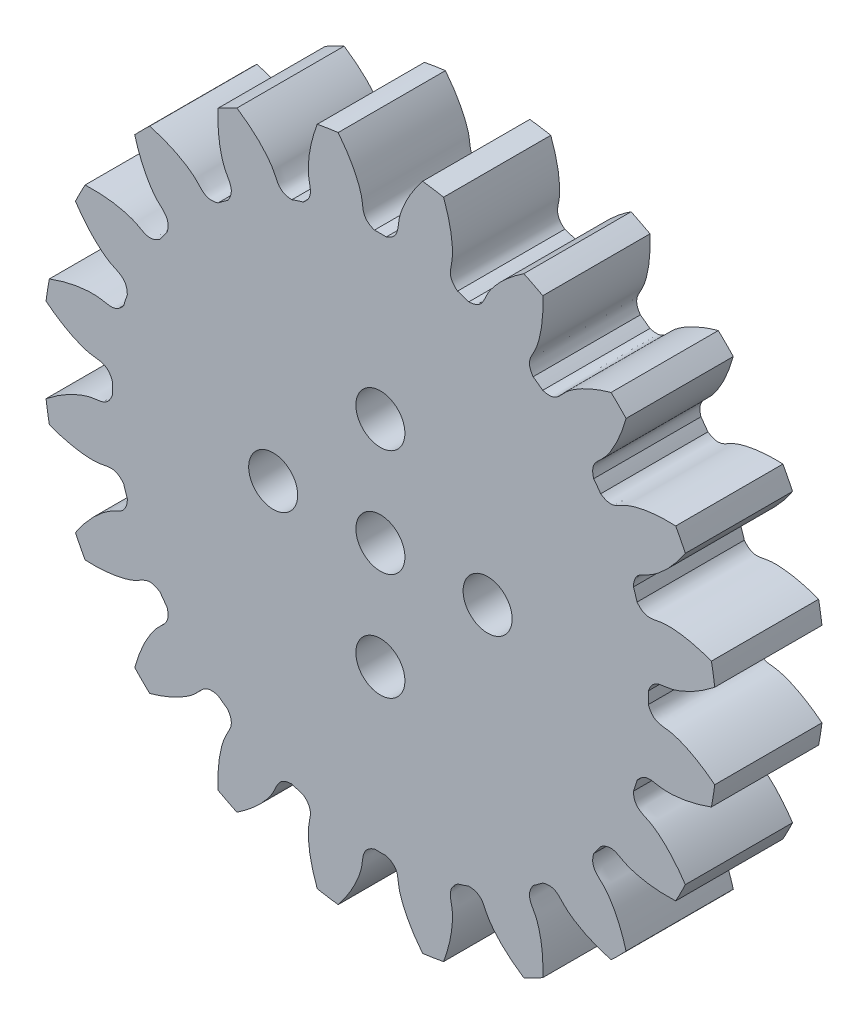
SolidWorks part; units mm, degrees
ref_plane "前视基准面" through (0, 0, 0) normal (0, 0, 1) x (1, 0, 0)
ref_plane "上视基准面" through (0, 0, 0) normal (0, 1, 0) x (1, 0, 0)
ref_plane "右视基准面" through (0, 0, 0) normal (1, 0, 0) x (0, 0, -1)
sketch "草图1" plane through (0, 0, 0) normal (0, 0, 1) x (1, 0, 0)
  circle A0 centre (0, 0) radius 22
extrude "凸台-拉伸1" add sketch "草图1" along normal blind 30
ref_axis "基准轴1" through (0, 0, -1.5) along (0, 0, 1)
sketch "草图2" plane through (0, 0, 0) normal (0, 0, 1) x (1, 0, 0)
  line L0 (0, 0) -> (0, 22) construction
  circle A0 centre (0, 0) radius 22 construction
  arc A1 (0.3866, 17.4957) -> (-0.3866, 17.4957) centre (0, 0) ccw
  arc A2 (6.3623, 24.9965) -> (-6.3623, 24.9965) centre (0, 0) ccw
  spline S0 degree 3 poles (0.3866, 17.4957) (1.2224, 17.787) (1.1142, 18.3742) (1.2258, 18.94) (1.2378, 18.9951) (1.2526, 19.0573) (1.2706, 19.1264) (1.292, 19.2024) (1.317, 19.2851) (1.3461, 19.3745) (1.3793, 19.4704) (1.4171, 19.5726) (1.4597, 19.6811) (1.5073, 19.7956) (1.5603, 19.9161) (1.6187, 20.0423) (1.683, 20.174) (1.7534, 20.3112) (1.83, 20.4535) (1.9132, 20.6008) (2.0031, 20.7529) (2.1, 20.9095) (2.204, 21.0705) (2.3155, 21.2356) (2.4346, 21.4046) (2.5615, 21.5772) (2.6964, 21.7533) (2.8395, 21.9324) (2.991, 22.1145) (3.1509, 22.2992) (3.3196, 22.4862) (3.4971, 22.6753) (3.6837, 22.8662) (3.8793, 23.0586) (4.0843, 23.2521) (4.2986, 23.4467) (4.5225, 23.6418) (4.7559, 23.8372) (4.9991, 24.0327) (5.2521, 24.2278) (5.515, 24.4223) (5.8829, 24.6833) (6.1679, 24.8727) (6.3623, 24.9965) knots 0 0 0 0 0.165916 0.170906 0.176664 0.183189 0.190482 0.198542 0.207371 0.216967 0.22733 0.238462 0.250361 0.263027 0.276462 0.290664 0.305634 0.321371 0.337876 0.355149 0.37319 0.391998 0.411574 0.431917 0.453028 0.474907 0.497554 0.520968 0.54515 0.570099 0.595817 0.622302 0.649554 0.677575 0.706363 0.735918 0.766242 0.797333 0.829191 0.861818 0.895212 0.929373 1 1 1 1
  spline S1 degree 3 poles (-0.3866, 17.4957) (-1.2224, 17.787) (-1.1142, 18.3742) (-1.2258, 18.94) (-1.2378, 18.9951) (-1.2526, 19.0573) (-1.2706, 19.1264) (-1.292, 19.2024) (-1.317, 19.2851) (-1.3461, 19.3745) (-1.3793, 19.4704) (-1.4171, 19.5726) (-1.4597, 19.6811) (-1.5073, 19.7956) (-1.5603, 19.9161) (-1.6187, 20.0423) (-1.683, 20.174) (-1.7534, 20.3112) (-1.83, 20.4535) (-1.9132, 20.6008) (-2.0031, 20.7529) (-2.1, 20.9095) (-2.204, 21.0705) (-2.3155, 21.2356) (-2.4346, 21.4046) (-2.5615, 21.5772) (-2.6964, 21.7533) (-2.8395, 21.9324) (-2.991, 22.1145) (-3.1509, 22.2992) (-3.3196, 22.4862) (-3.4971, 22.6753) (-3.6837, 22.8662) (-3.8793, 23.0586) (-4.0843, 23.2521) (-4.2986, 23.4467) (-4.5225, 23.6418) (-4.7559, 23.8372) (-4.9991, 24.0327) (-5.2521, 24.2278) (-5.515, 24.4223) (-5.8829, 24.6833) (-6.1679, 24.8727) (-6.3623, 24.9965) knots 0 0 0 0 0.165916 0.170906 0.176664 0.183189 0.190482 0.198542 0.207371 0.216967 0.22733 0.238462 0.250361 0.263027 0.276462 0.290664 0.305634 0.321371 0.337876 0.355149 0.37319 0.391998 0.411574 0.431917 0.453028 0.474907 0.497554 0.520968 0.54515 0.570099 0.595817 0.622302 0.649554 0.677575 0.706363 0.735918 0.766242 0.797333 0.829191 0.861818 0.895212 0.929373 1 1 1 1
extrude "切除-拉伸1" cut sketch "草图2" along normal through all
pattern_circular "阵列(圆周)1" count 20 every 18 about axis through (0, 0, -1.5) along (0, 0, 1) of "切除-拉伸1"
sketch "草图4" plane through (0, 0, 30) normal (0, 0, 1) x (1, 0, 0)
  line L0 (14.3305, 1.878) -> (0.1423, 3.6731)
  line L1 (0.1423, -3.7145) -> (14.354, -1.9038)
  line L2 (-14.5959, -1.8373) -> (0.1423, -3.7145)
  line L3 (0.1423, 3.6731) -> (-14.6311, 1.8342)
  circle A0 centre (0, 0) radius 0.8783 construction
  arc A1 (14.354, -1.9038) -> (14.3305, 1.878) centre (14.326, -0.013) ccw
  arc A2 (-14.6311, 1.8342) -> (-14.5959, -1.8373) centre (-14.4818, -0.0003) ccw
extrude "切除-拉伸2" [suppressed] cut sketch "草图4" against normal blind 3
sketch "草图6" plane through (0, 0, 0) normal (0, 0, -1) x (-1, 0, 0)
  arc A40 (5.7742, 16.52) -> (5.0388, 16.7589) centre (0, 0) ccw
  arc A41 (4.1243, 21.61) -> (2.7554, 21.8268) centre (0, 0) ccw
  arc A42 (0.3866, 17.4957) -> (-0.3866, 17.4957) centre (0, 0) ccw
  arc A43 (-2.7554, 21.8268) -> (-4.1243, 21.61) centre (0, 0) ccw
  arc A44 (-5.0388, 16.7589) -> (-5.7742, 16.52) centre (0, 0) ccw
  arc A45 (-9.3654, 19.907) -> (-10.6003, 19.2778) centre (0, 0) ccw
  arc A46 (-9.9709, 14.3816) -> (-10.5965, 13.9271) centre (0, 0) ccw
  arc A47 (-15.0586, 16.0386) -> (-16.0386, 15.0586) centre (0, 0) ccw
  arc A48 (-13.9271, 10.5965) -> (-14.3816, 9.9709) centre (0, 0) ccw
  arc A49 (-19.2778, 10.6003) -> (-19.907, 9.3654) centre (0, 0) ccw
  arc A50 (-16.52, 5.7742) -> (-16.7589, 5.0388) centre (0, 0) ccw
  arc A51 (-21.61, 4.1243) -> (-21.8268, 2.7554) centre (0, 0) ccw
  arc A52 (-17.4957, 0.3866) -> (-17.4957, -0.3866) centre (0, 0) ccw
  arc A53 (-21.8268, -2.7554) -> (-21.61, -4.1243) centre (0, 0) ccw
  arc A54 (-16.7589, -5.0388) -> (-16.52, -5.7742) centre (0, 0) ccw
  arc A55 (-19.907, -9.3654) -> (-19.2778, -10.6003) centre (0, 0) ccw
  arc A56 (-14.3816, -9.9709) -> (-13.9271, -10.5965) centre (0, 0) ccw
  arc A57 (-16.0386, -15.0586) -> (-15.0586, -16.0386) centre (0, 0) ccw
  arc A58 (-10.5965, -13.9271) -> (-9.9709, -14.3816) centre (0, 0) ccw
  arc A59 (-10.6003, -19.2778) -> (-9.3654, -19.907) centre (0, 0) ccw
  arc A60 (-5.7742, -16.52) -> (-5.0388, -16.7589) centre (0, 0) ccw
  arc A61 (-4.1243, -21.61) -> (-2.7554, -21.8268) centre (0, 0) ccw
  arc A62 (-0.3866, -17.4957) -> (0.3866, -17.4957) centre (0, 0) ccw
  arc A63 (2.7554, -21.8268) -> (4.1243, -21.61) centre (0, 0) ccw
  arc A64 (5.0388, -16.7589) -> (5.7742, -16.52) centre (0, 0) ccw
  arc A65 (9.3654, -19.907) -> (10.6003, -19.2778) centre (0, 0) ccw
  arc A66 (9.9709, -14.3816) -> (10.5965, -13.9271) centre (0, 0) ccw
  arc A67 (15.0586, -16.0386) -> (16.0386, -15.0586) centre (0, 0) ccw
  arc A68 (13.9271, -10.5965) -> (14.3816, -9.9709) centre (0, 0) ccw
  arc A69 (19.2778, -10.6003) -> (19.907, -9.3654) centre (0, 0) ccw
  arc A70 (16.52, -5.7742) -> (16.7589, -5.0388) centre (0, 0) ccw
  arc A71 (21.61, -4.1243) -> (21.8268, -2.7554) centre (0, 0) ccw
  arc A72 (17.4957, -0.3866) -> (17.4957, 0.3866) centre (0, 0) ccw
  arc A73 (21.8268, 2.7554) -> (21.61, 4.1243) centre (0, 0) ccw
  arc A74 (16.7589, 5.0388) -> (16.52, 5.7742) centre (0, 0) ccw
  arc A75 (19.907, 9.3654) -> (19.2778, 10.6003) centre (0, 0) ccw
  arc A76 (14.3816, 9.9709) -> (13.9271, 10.5965) centre (0, 0) ccw
  arc A77 (16.0386, 15.0586) -> (15.0586, 16.0386) centre (0, 0) ccw
  arc A78 (10.5965, 13.9271) -> (9.9709, 14.3816) centre (0, 0) ccw
  arc A79 (10.6003, 19.2778) -> (9.3654, 19.907) centre (0, 0) ccw
  arc A80 (5.7742, 16.52) -> (5.0388, 16.7589) centre (0, 0) ccw
  arc A81 (4.1243, 21.61) -> (2.7554, 21.8268) centre (0, 0) ccw
  arc A82 (0.3866, 17.4957) -> (-0.3866, 17.4957) centre (0, 0) ccw
  arc A83 (-2.7554, 21.8268) -> (-4.1243, 21.61) centre (0, 0) ccw
  arc A84 (-5.0388, 16.7589) -> (-5.7742, 16.52) centre (0, 0) ccw
  arc A85 (-9.3654, 19.907) -> (-10.6003, 19.2778) centre (0, 0) ccw
  arc A86 (-9.9709, 14.3816) -> (-10.5965, 13.9271) centre (0, 0) ccw
  arc A87 (-15.0586, 16.0386) -> (-16.0386, 15.0586) centre (0, 0) ccw
  arc A88 (-13.9271, 10.5965) -> (-14.3816, 9.9709) centre (0, 0) ccw
  arc A89 (-19.2778, 10.6003) -> (-19.907, 9.3654) centre (0, 0) ccw
  arc A90 (-16.52, 5.7742) -> (-16.7589, 5.0388) centre (0, 0) ccw
  arc A91 (-21.61, 4.1243) -> (-21.8268, 2.7554) centre (0, 0) ccw
  arc A92 (-17.4957, 0.3866) -> (-17.4957, -0.3866) centre (0, 0) ccw
  arc A93 (-21.8268, -2.7554) -> (-21.61, -4.1243) centre (0, 0) ccw
  arc A94 (-16.7589, -5.0388) -> (-16.52, -5.7742) centre (0, 0) ccw
  arc A95 (-19.907, -9.3654) -> (-19.2778, -10.6003) centre (0, 0) ccw
  arc A96 (-14.3816, -9.9709) -> (-13.9271, -10.5965) centre (0, 0) ccw
  arc A97 (-16.0386, -15.0586) -> (-15.0586, -16.0386) centre (0, 0) ccw
  arc A98 (-10.5965, -13.9271) -> (-9.9709, -14.3816) centre (0, 0) ccw
  arc A99 (-10.6003, -19.2778) -> (-9.3654, -19.907) centre (0, 0) ccw
  arc A100 (-5.7742, -16.52) -> (-5.0388, -16.7589) centre (0, 0) ccw
  arc A101 (-4.1243, -21.61) -> (-2.7554, -21.8268) centre (0, 0) ccw
  arc A102 (-0.3866, -17.4957) -> (0.3866, -17.4957) centre (0, 0) ccw
  arc A103 (2.7554, -21.8268) -> (4.1243, -21.61) centre (0, 0) ccw
  arc A104 (5.0388, -16.7589) -> (5.7742, -16.52) centre (0, 0) ccw
  arc A105 (9.3654, -19.907) -> (10.6003, -19.2778) centre (0, 0) ccw
  arc A106 (9.9709, -14.3816) -> (10.5965, -13.9271) centre (0, 0) ccw
  arc A107 (15.0586, -16.0386) -> (16.0386, -15.0586) centre (0, 0) ccw
  arc A108 (13.9271, -10.5965) -> (14.3816, -9.9709) centre (0, 0) ccw
  arc A109 (19.2778, -10.6003) -> (19.907, -9.3654) centre (0, 0) ccw
  arc A110 (16.52, -5.7742) -> (16.7589, -5.0388) centre (0, 0) ccw
  arc A111 (21.61, -4.1243) -> (21.8268, -2.7554) centre (0, 0) ccw
  arc A112 (17.4957, -0.3866) -> (17.4957, 0.3866) centre (0, 0) ccw
  arc A113 (21.8268, 2.7554) -> (21.61, 4.1243) centre (0, 0) ccw
  arc A114 (16.7589, 5.0388) -> (16.52, 5.7742) centre (0, 0) ccw
  arc A115 (19.907, 9.3654) -> (19.2778, 10.6003) centre (0, 0) ccw
  arc A116 (14.3816, 9.9709) -> (13.9271, 10.5965) centre (0, 0) ccw
  arc A117 (16.0386, 15.0586) -> (15.0586, 16.0386) centre (0, 0) ccw
  arc A118 (10.5965, 13.9271) -> (9.9709, 14.3816) centre (0, 0) ccw
  arc A119 (10.6003, 19.2778) -> (9.3654, 19.907) centre (0, 0) ccw
  spline S40 degree 3 poles (-3708.45, 1494.5416) (204.688, -113.6332) (40.2969, 43.5606) (8.612, 19.3644) (8.3225, 19.1244) (8.1035, 18.9276) (7.9087, 18.7415) (7.7679, 18.5988) (7.6102, 18.4289) (7.4979, 18.3006) (7.3961, 18.1768) (7.3285, 18.0912) (7.2672, 18.0103) (7.212, 17.9343) (7.1626, 17.8633) (7.1188, 17.7976) (7.0702, 17.7216) (7.029, 17.6528) (2.9985, 10.4296) (41.0631, -19.5683) (-3336.3667, 2212.5854) knots -11.584275 -11.584275 -11.584275 -11.584275 0.546972 0.588426 0.62681 0.662124 0.678629 0.709336 0.723538 0.749639 0.761538 0.77267 0.783033 0.792629 0.801458 0.809518 0.816811 0.829094 0.834084 3.350705 3.350705 3.350705 3.350705 only from (9.3654, 19.907) to (5.7742, 16.52)
  spline S41 degree 3 poles (4000.4369, -171.0805) (-44.7285, 8.305) (3.7044, 10.1997) (4.6895, 18.413) (4.6966, 18.4929) (4.702, 18.5829) (4.7051, 18.6618) (4.7069, 18.7482) (4.7069, 18.8422) (4.7048, 18.9437) (4.7005, 19.0526) (4.6909, 19.2127) (4.671, 19.4311) (4.6338, 19.7144) (4.5802, 20.0256) (4.508, 20.3639) (4.4148, 20.7281) (4.2986, 21.1171) (-9.4722, 61.2884) (-246.7896, 19.6625) (3881.4649, -959.8769) knots -2.350858 -2.350858 -2.350858 -2.350858 0.165916 0.170906 0.183189 0.190482 0.198542 0.207371 0.216967 0.22733 0.238462 0.250361 0.276462 0.305634 0.337876 0.37319 0.411574 0.453028 0.497554 13.418674 13.418674 13.418674 13.418674 only from (5.0388, 16.7589) to (4.1243, 21.61)
  spline S42 degree 3 poles (-3988.7843, 275.4194) (229.7845, -44.8196) (24.8636, 53.881) (2.2066, 21.0778) (2.0054, 20.7602) (1.8579, 20.5053) (1.7302, 20.2681) (1.6403, 20.0889) (1.5429, 19.8786) (1.4757, 19.7219) (1.4171, 19.5726) (1.3793, 19.4704) (1.3461, 19.3745) (1.317, 19.2851) (1.292, 19.2024) (1.2706, 19.1264) (1.2479, 19.0391) (1.2299, 18.9609) (-0.3711, 10.8457) (45.1002, -5.9213) (-3856.7998, 1073.2998) knots -11.584275 -11.584275 -11.584275 -11.584275 0.546972 0.588426 0.62681 0.662124 0.678629 0.709336 0.723538 0.749639 0.761538 0.77267 0.783033 0.792629 0.801458 0.809518 0.816811 0.829094 0.834084 3.350705 3.350705 3.350705 3.350705 only from (2.7554, 21.8268) to (0.3866, 17.4957)
  spline S43 degree 3 poles (3857.5084, 1073.4958) (-45.1057, -5.9234) (0.3712, 10.8453) (-1.2299, 18.9609) (-1.2479, 19.0391) (-1.2706, 19.1264) (-1.292, 19.2024) (-1.317, 19.2851) (-1.3461, 19.3745) (-1.3793, 19.4704) (-1.4171, 19.5726) (-1.4757, 19.7219) (-1.5621, 19.9235) (-1.6851, 20.1814) (-1.8322, 20.4609) (-2.0054, 20.7602) (-2.2066, 21.0778) (-2.4373, 21.4119) (-27.9477, 55.3617) (-240.7869, -57.562) (3988.1108, 286.5414) knots -2.350858 -2.350858 -2.350858 -2.350858 0.165916 0.170906 0.183189 0.190482 0.198542 0.207371 0.216967 0.22733 0.238462 0.250361 0.276462 0.305634 0.337876 0.37319 0.411574 0.453028 0.497554 13.418674 13.418674 13.418674 13.418674 only from (-0.3866, 17.4957) to (-2.7554, 21.8268)
  spline S44 degree 3 poles (-3878.6685, -970.6627) (232.388, 28.3814) (6.9966, 58.9272) (-4.4148, 20.7281) (-4.508, 20.3639) (-4.5695, 20.0759) (-4.6177, 19.8108) (-4.6478, 19.6126) (-4.6755, 19.3824) (-4.6909, 19.2127) (-4.7005, 19.0526) (-4.7048, 18.9437) (-4.7069, 18.8422) (-4.7069, 18.7482) (-4.7051, 18.6618) (-4.702, 18.5829) (-4.6966, 18.4929) (-4.6895, 18.413) (-3.7045, 10.2002) (44.7226, 8.3052) (-3999.7024, -171.0479) knots -11.584275 -11.584275 -11.584275 -11.584275 0.546972 0.588426 0.62681 0.662124 0.678629 0.709336 0.723538 0.749639 0.761538 0.77267 0.783033 0.792629 0.801458 0.809518 0.816811 0.829094 0.834084 3.350705 3.350705 3.350705 3.350705 only from (-4.1243, 21.61) to (-5.0388, 16.7589)
  spline S45 degree 3 poles (3336.9801, 2212.9908) (-41.0677, -19.5719) (-2.9983, 10.4292) (-7.029, 17.6528) (-7.0702, 17.7216) (-7.1188, 17.7976) (-7.1626, 17.8633) (-7.212, 17.9343) (-7.2672, 18.0103) (-7.3285, 18.0912) (-7.3961, 18.1768) (-7.4979, 18.3006) (-7.6424, 18.4656) (-7.839, 18.673) (-8.0653, 18.8932) (-8.3225, 19.1244) (-8.612, 19.3644) (-8.9347, 19.6108) (-43.6876, 44.0158) (-211.2143, -129.152) (3704.3726, 1504.9111) knots -2.350858 -2.350858 -2.350858 -2.350858 0.165916 0.170906 0.183189 0.190482 0.198542 0.207371 0.216967 0.22733 0.238462 0.250361 0.276462 0.305634 0.337876 0.37319 0.411574 0.453028 0.497554 13.418674 13.418674 13.418674 13.418674 only from (-5.7742, 16.52) to (-9.3654, 19.907)
  spline S46 degree 3 poles (-3388.8817, -2121.7296) (212.2438, 98.8041) (-11.5554, 58.2051) (-10.6041, 18.3493) (-10.5801, 17.9741) (-10.5496, 17.6812) (-10.5135, 17.4143) (-10.4809, 17.2164) (-10.4361, 16.989) (-10.3984, 16.8228) (-10.358, 16.6676) (-10.3285, 16.5626) (-10.2991, 16.4655) (-10.27, 16.3761) (-10.2417, 16.2944) (-10.2143, 16.2204) (-10.1813, 16.1364) (-10.1499, 16.0626) (-6.6752, 8.5562) (39.9673, 21.7188) (-3751.0863, -1398.6523) knots -11.584275 -11.584275 -11.584275 -11.584275 0.546972 0.588426 0.62681 0.662124 0.678629 0.709336 0.723538 0.749639 0.761538 0.77267 0.783033 0.792629 0.801458 0.809518 0.816811 0.829094 0.834084 3.350705 3.350705 3.350705 3.350705 only from (-10.6003, 19.2778) to (-9.9709, 14.3816)
  spline S47 degree 3 poles (2489.8049, 3135.8629) (-33.0096, -31.3046) (-6.0743, 8.9922) (-12.14, 14.6168) (-12.2005, 14.6694) (-12.2701, 14.7267) (-12.3321, 14.7757) (-12.401, 14.8279) (-12.477, 14.8831) (-12.5603, 14.9411) (-12.651, 15.0016) (-12.7861, 15.088) (-12.9745, 15.2003) (-13.2256, 15.3367) (-13.5089, 15.4762) (-13.825, 15.6166) (-14.1744, 15.7553) (-14.5574, 15.89) (-55.151, 28.3613) (-160.9666, -188.0996) (3058.0246, 2575.9696) knots -2.350858 -2.350858 -2.350858 -2.350858 0.165916 0.170906 0.183189 0.190482 0.198542 0.207371 0.216967 0.22733 0.238462 0.250361 0.276462 0.305634 0.337876 0.37319 0.411574 0.453028 0.497554 13.418674 13.418674 13.418674 13.418674 only from (-10.5965, 13.9271) to (-15.0586, 16.0386)
  spline S48 degree 3 poles (-2567.3676, -3065.1068) (171.3237, 159.5553) (-28.9762, 51.7856) (-15.7553, 14.1744) (-15.6166, 13.825) (-15.4971, 13.5558) (-15.3803, 13.3131) (-15.2881, 13.135) (-15.1752, 12.9325) (-15.088, 12.7861) (-15.0016, 12.651) (-14.9411, 12.5603) (-14.8831, 12.477) (-14.8279, 12.401) (-14.7757, 12.3321) (-14.7267, 12.2701) (-14.6694, 12.2005) (-14.6168, 12.14) (-8.9925, 6.0747) (31.2997, 33.0064) (-3135.2878, -2489.3468) knots -11.584275 -11.584275 -11.584275 -11.584275 0.546972 0.588426 0.62681 0.662124 0.678629 0.709336 0.723538 0.749639 0.761538 0.77267 0.783033 0.792629 0.801458 0.809518 0.816811 0.829094 0.834084 3.350705 3.350705 3.350705 3.350705 only from (-16.0386, 15.0586) to (-13.9271, 10.5965)
  spline S49 degree 3 poles (1398.9102, 3751.7748) (-21.7204, -39.973) (-8.5558, 6.675) (-16.0626, 10.1499) (-16.1364, 10.1813) (-16.2204, 10.2143) (-16.2944, 10.2417) (-16.3761, 10.27) (-16.4655, 10.2991) (-16.5626, 10.3285) (-16.6676, 10.358) (-16.8228, 10.3984) (-17.0366, 10.447) (-17.3176, 10.4991) (-17.6301, 10.5443) (-17.9741, 10.5801) (-18.3493, 10.6041) (-18.7552, 10.6138) (-61.2158, 9.9306) (-94.9623, -228.6348) (2112.3358, 3394.8742) knots -2.350858 -2.350858 -2.350858 -2.350858 0.165916 0.170906 0.183189 0.190482 0.198542 0.207371 0.216967 0.22733 0.238462 0.250361 0.276462 0.305634 0.337876 0.37319 0.411574 0.453028 0.497554 13.418674 13.418674 13.418674 13.418674 only from (-14.3816, 9.9709) to (-19.2778, 10.6003)
  spline S50 degree 3 poles (-1494.5416, -3708.45) (113.6332, 204.688) (-43.5606, 40.2969) (-19.3644, 8.612) (-19.1244, 8.3225) (-18.9276, 8.1035) (-18.7415, 7.9087) (-18.5988, 7.7679) (-18.4289, 7.6102) (-18.3006, 7.4979) (-18.1768, 7.3961) (-18.0912, 7.3285) (-18.0103, 7.2672) (-17.9343, 7.212) (-17.8633, 7.1626) (-17.7976, 7.1188) (-17.7216, 7.0702) (-17.6528, 7.029) (-10.4296, 2.9985) (19.5683, 41.0631) (-2212.5854, -3336.3667) knots -11.584275 -11.584275 -11.584275 -11.584275 0.546972 0.588426 0.62681 0.662124 0.678629 0.709336 0.723538 0.749639 0.761538 0.77267 0.783033 0.792629 0.801458 0.809518 0.816811 0.829094 0.834084 3.350705 3.350705 3.350705 3.350705 only from (-19.907, 9.3654) to (-16.52, 5.7742)
  spline S51 degree 3 poles (171.0805, 4000.4369) (-8.305, -44.7285) (-10.1997, 3.7044) (-18.413, 4.6895) (-18.4929, 4.6966) (-18.5829, 4.702) (-18.6618, 4.7051) (-18.7482, 4.7069) (-18.8422, 4.7069) (-18.9437, 4.7048) (-19.0526, 4.7005) (-19.2127, 4.6909) (-19.4311, 4.671) (-19.7144, 4.6338) (-20.0256, 4.5802) (-20.3639, 4.508) (-20.7281, 4.4148) (-21.1171, 4.2986) (-61.2884, -9.4722) (-19.6625, -246.7896) (959.8769, 3881.4649) knots -2.350858 -2.350858 -2.350858 -2.350858 0.165916 0.170906 0.183189 0.190482 0.198542 0.207371 0.216967 0.22733 0.238462 0.250361 0.276462 0.305634 0.337876 0.37319 0.411574 0.453028 0.497554 13.418674 13.418674 13.418674 13.418674 only from (-16.7589, 5.0388) to (-21.61, 4.1243)
  spline S52 degree 3 poles (-275.4194, -3988.7843) (44.8196, 229.7845) (-53.881, 24.8636) (-21.0778, 2.2066) (-20.7602, 2.0054) (-20.5053, 1.8579) (-20.2681, 1.7302) (-20.0889, 1.6403) (-19.8786, 1.5429) (-19.7219, 1.4757) (-19.5726, 1.4171) (-19.4704, 1.3793) (-19.3745, 1.3461) (-19.2851, 1.317) (-19.2024, 1.292) (-19.1264, 1.2706) (-19.0391, 1.2479) (-18.9609, 1.2299) (-10.8457, -0.3711) (5.9213, 45.1002) (-1073.2998, -3856.7998) knots -11.584275 -11.584275 -11.584275 -11.584275 0.546972 0.588426 0.62681 0.662124 0.678629 0.709336 0.723538 0.749639 0.761538 0.77267 0.783033 0.792629 0.801458 0.809518 0.816811 0.829094 0.834084 3.350705 3.350705 3.350705 3.350705 only from (-21.8268, 2.7554) to (-17.4957, 0.3866)
  spline S53 degree 3 poles (-1073.4958, 3857.5084) (5.9234, -45.1057) (-10.8453, 0.3712) (-18.9609, -1.2299) (-19.0391, -1.2479) (-19.1264, -1.2706) (-19.2024, -1.292) (-19.2851, -1.317) (-19.3745, -1.3461) (-19.4704, -1.3793) (-19.5726, -1.4171) (-19.7219, -1.4757) (-19.9235, -1.5621) (-20.1814, -1.6851) (-20.4609, -1.8322) (-20.7602, -2.0054) (-21.0778, -2.2066) (-21.4119, -2.4373) (-55.3617, -27.9477) (57.562, -240.7869) (-286.5415, 3988.1108) knots -2.350858 -2.350858 -2.350858 -2.350858 0.165916 0.170906 0.183189 0.190482 0.198542 0.207371 0.216967 0.22733 0.238462 0.250361 0.276462 0.305634 0.337876 0.37319 0.411574 0.453028 0.497554 13.418674 13.418674 13.418674 13.418674 only from (-17.4957, -0.3866) to (-21.8268, -2.7554)
  spline S54 degree 3 poles (970.6627, -3878.6685) (-28.3814, 232.388) (-58.9272, 6.9966) (-20.7281, -4.4148) (-20.3639, -4.508) (-20.0759, -4.5695) (-19.8108, -4.6177) (-19.6126, -4.6478) (-19.3824, -4.6755) (-19.2127, -4.6909) (-19.0526, -4.7005) (-18.9437, -4.7048) (-18.8422, -4.7069) (-18.7482, -4.7069) (-18.6618, -4.7051) (-18.5829, -4.702) (-18.4929, -4.6966) (-18.413, -4.6895) (-10.2002, -3.7045) (-8.3052, 44.7226) (171.0479, -3999.7024) knots -11.584275 -11.584275 -11.584275 -11.584275 0.546972 0.588426 0.62681 0.662124 0.678629 0.709336 0.723538 0.749639 0.761538 0.77267 0.783033 0.792629 0.801458 0.809518 0.816811 0.829094 0.834084 3.350705 3.350705 3.350705 3.350705 only from (-21.61, -4.1243) to (-16.7589, -5.0388)
  spline S55 degree 3 poles (-2212.9908, 3336.9801) (19.5719, -41.0677) (-10.4292, -2.9983) (-17.6528, -7.029) (-17.7216, -7.0702) (-17.7976, -7.1188) (-17.8633, -7.1626) (-17.9343, -7.212) (-18.0103, -7.2672) (-18.0912, -7.3285) (-18.1768, -7.3961) (-18.3006, -7.4979) (-18.4656, -7.6424) (-18.673, -7.839) (-18.8932, -8.0653) (-19.1244, -8.3225) (-19.3644, -8.612) (-19.6108, -8.9347) (-44.0158, -43.6876) (129.152, -211.2143) (-1504.9111, 3704.3726) knots -2.350858 -2.350858 -2.350858 -2.350858 0.165916 0.170906 0.183189 0.190482 0.198542 0.207371 0.216967 0.22733 0.238462 0.250361 0.276462 0.305634 0.337876 0.37319 0.411574 0.453028 0.497554 13.418674 13.418674 13.418674 13.418674 only from (-16.52, -5.7742) to (-19.907, -9.3654)
  spline S56 degree 3 poles (2121.7296, -3388.8817) (-98.8041, 212.2438) (-58.2051, -11.5554) (-18.3493, -10.6041) (-17.9741, -10.5801) (-17.6812, -10.5496) (-17.4143, -10.5135) (-17.2164, -10.4809) (-16.989, -10.4361) (-16.8228, -10.3984) (-16.6676, -10.358) (-16.5626, -10.3285) (-16.4655, -10.2991) (-16.3761, -10.27) (-16.2944, -10.2417) (-16.2204, -10.2143) (-16.1364, -10.1813) (-16.0626, -10.1499) (-8.5562, -6.6752) (-21.7188, 39.9673) (1398.6523, -3751.0863) knots -11.584275 -11.584275 -11.584275 -11.584275 0.546972 0.588426 0.62681 0.662124 0.678629 0.709336 0.723538 0.749639 0.761538 0.77267 0.783033 0.792629 0.801458 0.809518 0.816811 0.829094 0.834084 3.350705 3.350705 3.350705 3.350705 only from (-19.2778, -10.6003) to (-14.3816, -9.9709)
  spline S57 degree 3 poles (-3135.8629, 2489.8049) (31.3046, -33.0096) (-8.9922, -6.0743) (-14.6168, -12.14) (-14.6694, -12.2005) (-14.7267, -12.2701) (-14.7757, -12.3321) (-14.8279, -12.401) (-14.8831, -12.477) (-14.9411, -12.5603) (-15.0016, -12.651) (-15.088, -12.7861) (-15.2003, -12.9745) (-15.3367, -13.2256) (-15.4762, -13.5089) (-15.6166, -13.825) (-15.7553, -14.1744) (-15.89, -14.5574) (-28.3613, -55.151) (188.0996, -160.9666) (-2575.9696, 3058.0246) knots -2.350858 -2.350858 -2.350858 -2.350858 0.165916 0.170906 0.183189 0.190482 0.198542 0.207371 0.216967 0.22733 0.238462 0.250361 0.276462 0.305634 0.337876 0.37319 0.411574 0.453028 0.497554 13.418674 13.418674 13.418674 13.418674 only from (-13.9271, -10.5965) to (-16.0386, -15.0586)
  spline S58 degree 3 poles (3065.1068, -2567.3676) (-159.5553, 171.3237) (-51.7856, -28.9762) (-14.1744, -15.7553) (-13.825, -15.6166) (-13.5558, -15.4971) (-13.3131, -15.3803) (-13.135, -15.2881) (-12.9325, -15.1752) (-12.7861, -15.088) (-12.651, -15.0016) (-12.5603, -14.9411) (-12.477, -14.8831) (-12.401, -14.8279) (-12.3321, -14.7757) (-12.2701, -14.7267) (-12.2005, -14.6694) (-12.14, -14.6168) (-6.0747, -8.9925) (-33.0064, 31.2997) (2489.3468, -3135.2878) knots -11.584275 -11.584275 -11.584275 -11.584275 0.546972 0.588426 0.62681 0.662124 0.678629 0.709336 0.723538 0.749639 0.761538 0.77267 0.783033 0.792629 0.801458 0.809518 0.816811 0.829094 0.834084 3.350705 3.350705 3.350705 3.350705 only from (-15.0586, -16.0386) to (-10.5965, -13.9271)
  spline S59 degree 3 poles (-3751.7748, 1398.9102) (39.973, -21.7204) (-6.675, -8.5558) (-10.1499, -16.0626) (-10.1813, -16.1364) (-10.2143, -16.2204) (-10.2417, -16.2944) (-10.27, -16.3761) (-10.2991, -16.4655) (-10.3285, -16.5626) (-10.358, -16.6676) (-10.3984, -16.8228) (-10.447, -17.0366) (-10.4991, -17.3176) (-10.5443, -17.6301) (-10.5801, -17.9741) (-10.6041, -18.3493) (-10.6138, -18.7552) (-9.9306, -61.2158) (228.6348, -94.9623) (-3394.8742, 2112.3358) knots -2.350858 -2.350858 -2.350858 -2.350858 0.165916 0.170906 0.183189 0.190482 0.198542 0.207371 0.216967 0.22733 0.238462 0.250361 0.276462 0.305634 0.337876 0.37319 0.411574 0.453028 0.497554 13.418674 13.418674 13.418674 13.418674 only from (-9.9709, -14.3816) to (-10.6003, -19.2778)
  spline S60 degree 3 poles (3708.45, -1494.5416) (-204.688, 113.6332) (-40.2969, -43.5606) (-8.612, -19.3644) (-8.3225, -19.1244) (-8.1035, -18.9276) (-7.9087, -18.7415) (-7.7679, -18.5988) (-7.6102, -18.4289) (-7.4979, -18.3006) (-7.3961, -18.1768) (-7.3285, -18.0912) (-7.2672, -18.0103) (-7.212, -17.9343) (-7.1626, -17.8633) (-7.1188, -17.7976) (-7.0702, -17.7216) (-7.029, -17.6528) (-2.9985, -10.4296) (-41.0631, 19.5683) (3336.3667, -2212.5854) knots -11.584275 -11.584275 -11.584275 -11.584275 0.546972 0.588426 0.62681 0.662124 0.678629 0.709336 0.723538 0.749639 0.761538 0.77267 0.783033 0.792629 0.801458 0.809518 0.816811 0.829094 0.834084 3.350705 3.350705 3.350705 3.350705 only from (-9.3654, -19.907) to (-5.7742, -16.52)
  spline S61 degree 3 poles (-4000.4369, 171.0805) (44.7285, -8.305) (-3.7044, -10.1997) (-4.6895, -18.413) (-4.6966, -18.4929) (-4.702, -18.5829) (-4.7051, -18.6618) (-4.7069, -18.7482) (-4.7069, -18.8422) (-4.7048, -18.9437) (-4.7005, -19.0526) (-4.6909, -19.2127) (-4.671, -19.4311) (-4.6338, -19.7144) (-4.5802, -20.0256) (-4.508, -20.3639) (-4.4148, -20.7281) (-4.2986, -21.1171) (9.4722, -61.2884) (246.7896, -19.6625) (-3881.4649, 959.8769) knots -2.350858 -2.350858 -2.350858 -2.350858 0.165916 0.170906 0.183189 0.190482 0.198542 0.207371 0.216967 0.22733 0.238462 0.250361 0.276462 0.305634 0.337876 0.37319 0.411574 0.453028 0.497554 13.418674 13.418674 13.418674 13.418674 only from (-5.0388, -16.7589) to (-4.1243, -21.61)
  spline S62 degree 3 poles (3988.7843, -275.4194) (-229.7845, 44.8196) (-24.8636, -53.881) (-2.2066, -21.0778) (-2.0054, -20.7602) (-1.8579, -20.5053) (-1.7302, -20.2681) (-1.6403, -20.0889) (-1.5429, -19.8786) (-1.4757, -19.7219) (-1.4171, -19.5726) (-1.3793, -19.4704) (-1.3461, -19.3745) (-1.317, -19.2851) (-1.292, -19.2024) (-1.2706, -19.1264) (-1.2479, -19.0391) (-1.2299, -18.9609) (0.3711, -10.8457) (-45.1002, 5.9213) (3856.7998, -1073.2998) knots -11.584275 -11.584275 -11.584275 -11.584275 0.546972 0.588426 0.62681 0.662124 0.678629 0.709336 0.723538 0.749639 0.761538 0.77267 0.783033 0.792629 0.801458 0.809518 0.816811 0.829094 0.834084 3.350705 3.350705 3.350705 3.350705 only from (-2.7554, -21.8268) to (-0.3866, -17.4957)
  spline S63 degree 3 poles (-3857.5084, -1073.4958) (45.1057, 5.9234) (-0.3712, -10.8453) (1.2299, -18.9609) (1.2479, -19.0391) (1.2706, -19.1264) (1.292, -19.2024) (1.317, -19.2851) (1.3461, -19.3745) (1.3793, -19.4704) (1.4171, -19.5726) (1.4757, -19.7219) (1.5621, -19.9235) (1.6851, -20.1814) (1.8322, -20.4609) (2.0054, -20.7602) (2.2066, -21.0778) (2.4373, -21.4119) (27.9477, -55.3617) (240.7869, 57.562) (-3988.1108, -286.5415) knots -2.350858 -2.350858 -2.350858 -2.350858 0.165916 0.170906 0.183189 0.190482 0.198542 0.207371 0.216967 0.22733 0.238462 0.250361 0.276462 0.305634 0.337876 0.37319 0.411574 0.453028 0.497554 13.418674 13.418674 13.418674 13.418674 only from (0.3866, -17.4957) to (2.7554, -21.8268)
  spline S64 degree 3 poles (3878.6685, 970.6627) (-232.388, -28.3814) (-6.9966, -58.9272) (4.4148, -20.7281) (4.508, -20.3639) (4.5695, -20.0759) (4.6177, -19.8108) (4.6478, -19.6126) (4.6755, -19.3824) (4.6909, -19.2127) (4.7005, -19.0526) (4.7048, -18.9437) (4.7069, -18.8422) (4.7069, -18.7482) (4.7051, -18.6618) (4.702, -18.5829) (4.6966, -18.4929) (4.6895, -18.413) (3.7045, -10.2002) (-44.7226, -8.3052) (3999.7024, 171.0479) knots -11.584275 -11.584275 -11.584275 -11.584275 0.546972 0.588426 0.62681 0.662124 0.678629 0.709336 0.723538 0.749639 0.761538 0.77267 0.783033 0.792629 0.801458 0.809518 0.816811 0.829094 0.834084 3.350705 3.350705 3.350705 3.350705 only from (4.1243, -21.61) to (5.0388, -16.7589)
  spline S65 degree 3 poles (-3336.9801, -2212.9908) (41.0677, 19.5719) (2.9983, -10.4292) (7.029, -17.6528) (7.0702, -17.7216) (7.1188, -17.7976) (7.1626, -17.8633) (7.212, -17.9343) (7.2672, -18.0103) (7.3285, -18.0912) (7.3961, -18.1768) (7.4979, -18.3006) (7.6424, -18.4656) (7.839, -18.673) (8.0653, -18.8932) (8.3225, -19.1244) (8.612, -19.3644) (8.9347, -19.6108) (43.6876, -44.0158) (211.2143, 129.152) (-3704.3726, -1504.9111) knots -2.350858 -2.350858 -2.350858 -2.350858 0.165916 0.170906 0.183189 0.190482 0.198542 0.207371 0.216967 0.22733 0.238462 0.250361 0.276462 0.305634 0.337876 0.37319 0.411574 0.453028 0.497554 13.418674 13.418674 13.418674 13.418674 only from (5.7742, -16.52) to (9.3654, -19.907)
  spline S66 degree 3 poles (3388.8817, 2121.7296) (-212.2438, -98.8041) (11.5554, -58.2051) (10.6041, -18.3493) (10.5801, -17.9741) (10.5496, -17.6812) (10.5135, -17.4143) (10.4809, -17.2164) (10.4361, -16.989) (10.3984, -16.8228) (10.358, -16.6676) (10.3285, -16.5626) (10.2991, -16.4655) (10.27, -16.3761) (10.2417, -16.2944) (10.2143, -16.2204) (10.1813, -16.1364) (10.1499, -16.0626) (6.6752, -8.5562) (-39.9673, -21.7188) (3751.0863, 1398.6523) knots -11.584275 -11.584275 -11.584275 -11.584275 0.546972 0.588426 0.62681 0.662124 0.678629 0.709336 0.723538 0.749639 0.761538 0.77267 0.783033 0.792629 0.801458 0.809518 0.816811 0.829094 0.834084 3.350705 3.350705 3.350705 3.350705 only from (10.6003, -19.2778) to (9.9709, -14.3816)
  spline S67 degree 3 poles (-2489.8049, -3135.8629) (33.0096, 31.3046) (6.0743, -8.9922) (12.14, -14.6168) (12.2005, -14.6694) (12.2701, -14.7267) (12.3321, -14.7757) (12.401, -14.8279) (12.477, -14.8831) (12.5603, -14.9411) (12.651, -15.0016) (12.7861, -15.088) (12.9745, -15.2003) (13.2256, -15.3367) (13.5089, -15.4762) (13.825, -15.6166) (14.1744, -15.7553) (14.5574, -15.89) (55.151, -28.3613) (160.9666, 188.0996) (-3058.0246, -2575.9696) knots -2.350858 -2.350858 -2.350858 -2.350858 0.165916 0.170906 0.183189 0.190482 0.198542 0.207371 0.216967 0.22733 0.238462 0.250361 0.276462 0.305634 0.337876 0.37319 0.411574 0.453028 0.497554 13.418674 13.418674 13.418674 13.418674 only from (10.5965, -13.9271) to (15.0586, -16.0386)
  spline S68 degree 3 poles (2567.3676, 3065.1068) (-171.3237, -159.5553) (28.9762, -51.7856) (15.7553, -14.1744) (15.6166, -13.825) (15.4971, -13.5558) (15.3803, -13.3131) (15.2881, -13.135) (15.1752, -12.9325) (15.088, -12.7861) (15.0016, -12.651) (14.9411, -12.5603) (14.8831, -12.477) (14.8279, -12.401) (14.7757, -12.3321) (14.7267, -12.2701) (14.6694, -12.2005) (14.6168, -12.14) (8.9925, -6.0747) (-31.2997, -33.0064) (3135.2878, 2489.3468) knots -11.584275 -11.584275 -11.584275 -11.584275 0.546972 0.588426 0.62681 0.662124 0.678629 0.709336 0.723538 0.749639 0.761538 0.77267 0.783033 0.792629 0.801458 0.809518 0.816811 0.829094 0.834084 3.350705 3.350705 3.350705 3.350705 only from (16.0386, -15.0586) to (13.9271, -10.5965)
  spline S69 degree 3 poles (-1398.9102, -3751.7748) (21.7204, 39.973) (8.5558, -6.675) (16.0626, -10.1499) (16.1364, -10.1813) (16.2204, -10.2143) (16.2944, -10.2417) (16.3761, -10.27) (16.4655, -10.2991) (16.5626, -10.3285) (16.6676, -10.358) (16.8228, -10.3984) (17.0366, -10.447) (17.3176, -10.4991) (17.6301, -10.5443) (17.9741, -10.5801) (18.3493, -10.6041) (18.7552, -10.6138) (61.2158, -9.9306) (94.9623, 228.6348) (-2112.3358, -3394.8742) knots -2.350858 -2.350858 -2.350858 -2.350858 0.165916 0.170906 0.183189 0.190482 0.198542 0.207371 0.216967 0.22733 0.238462 0.250361 0.276462 0.305634 0.337876 0.37319 0.411574 0.453028 0.497554 13.418674 13.418674 13.418674 13.418674 only from (14.3816, -9.9709) to (19.2778, -10.6003)
  spline S70 degree 3 poles (1494.5416, 3708.45) (-113.6332, -204.688) (43.5606, -40.2969) (19.3644, -8.612) (19.1244, -8.3225) (18.9276, -8.1035) (18.7415, -7.9087) (18.5988, -7.7679) (18.4289, -7.6102) (18.3006, -7.4979) (18.1768, -7.3961) (18.0912, -7.3285) (18.0103, -7.2672) (17.9343, -7.212) (17.8633, -7.1626) (17.7976, -7.1188) (17.7216, -7.0702) (17.6528, -7.029) (10.4296, -2.9985) (-19.5683, -41.0631) (2212.5854, 3336.3667) knots -11.584275 -11.584275 -11.584275 -11.584275 0.546972 0.588426 0.62681 0.662124 0.678629 0.709336 0.723538 0.749639 0.761538 0.77267 0.783033 0.792629 0.801458 0.809518 0.816811 0.829094 0.834084 3.350705 3.350705 3.350705 3.350705 only from (19.907, -9.3654) to (16.52, -5.7742)
  spline S71 degree 3 poles (-171.0805, -4000.4369) (8.305, 44.7285) (10.1997, -3.7044) (18.413, -4.6895) (18.4929, -4.6966) (18.5829, -4.702) (18.6618, -4.7051) (18.7482, -4.7069) (18.8422, -4.7069) (18.9437, -4.7048) (19.0526, -4.7005) (19.2127, -4.6909) (19.4311, -4.671) (19.7144, -4.6338) (20.0256, -4.5802) (20.3639, -4.508) (20.7281, -4.4148) (21.1171, -4.2986) (61.2884, 9.4722) (19.6625, 246.7896) (-959.8769, -3881.4649) knots -2.350858 -2.350858 -2.350858 -2.350858 0.165916 0.170906 0.183189 0.190482 0.198542 0.207371 0.216967 0.22733 0.238462 0.250361 0.276462 0.305634 0.337876 0.37319 0.411574 0.453028 0.497554 13.418674 13.418674 13.418674 13.418674 only from (16.7589, -5.0388) to (21.61, -4.1243)
  spline S72 degree 3 poles (275.4194, 3988.7843) (-44.8196, -229.7845) (53.881, -24.8636) (21.0778, -2.2066) (20.7602, -2.0054) (20.5053, -1.8579) (20.2681, -1.7302) (20.0889, -1.6403) (19.8786, -1.5429) (19.7219, -1.4757) (19.5726, -1.4171) (19.4704, -1.3793) (19.3745, -1.3461) (19.2851, -1.317) (19.2024, -1.292) (19.1264, -1.2706) (19.0391, -1.2479) (18.9609, -1.2299) (10.8457, 0.3711) (-5.9213, -45.1002) (1073.2998, 3856.7998) knots -11.584275 -11.584275 -11.584275 -11.584275 0.546972 0.588426 0.62681 0.662124 0.678629 0.709336 0.723538 0.749639 0.761538 0.77267 0.783033 0.792629 0.801458 0.809518 0.816811 0.829094 0.834084 3.350705 3.350705 3.350705 3.350705 only from (21.8268, -2.7554) to (17.4957, -0.3866)
  spline S73 degree 3 poles (1073.4958, -3857.5084) (-5.9234, 45.1057) (10.8453, -0.3712) (18.9609, 1.2299) (19.0391, 1.2479) (19.1264, 1.2706) (19.2024, 1.292) (19.2851, 1.317) (19.3745, 1.3461) (19.4704, 1.3793) (19.5726, 1.4171) (19.7219, 1.4757) (19.9235, 1.5621) (20.1814, 1.6851) (20.4609, 1.8322) (20.7602, 2.0054) (21.0778, 2.2066) (21.4119, 2.4373) (55.3617, 27.9477) (-57.562, 240.7869) (286.5414, -3988.1108) knots -2.350858 -2.350858 -2.350858 -2.350858 0.165916 0.170906 0.183189 0.190482 0.198542 0.207371 0.216967 0.22733 0.238462 0.250361 0.276462 0.305634 0.337876 0.37319 0.411574 0.453028 0.497554 13.418674 13.418674 13.418674 13.418674 only from (17.4957, 0.3866) to (21.8268, 2.7554)
  spline S74 degree 3 poles (-970.6627, 3878.6685) (28.3814, -232.388) (58.9272, -6.9966) (20.7281, 4.4148) (20.3639, 4.508) (20.0759, 4.5695) (19.8108, 4.6177) (19.6126, 4.6478) (19.3824, 4.6755) (19.2127, 4.6909) (19.0526, 4.7005) (18.9437, 4.7048) (18.8422, 4.7069) (18.7482, 4.7069) (18.6618, 4.7051) (18.5829, 4.702) (18.4929, 4.6966) (18.413, 4.6895) (10.2002, 3.7045) (8.3052, -44.7226) (-171.0479, 3999.7024) knots -11.584275 -11.584275 -11.584275 -11.584275 0.546972 0.588426 0.62681 0.662124 0.678629 0.709336 0.723538 0.749639 0.761538 0.77267 0.783033 0.792629 0.801458 0.809518 0.816811 0.829094 0.834084 3.350705 3.350705 3.350705 3.350705 only from (21.61, 4.1243) to (16.7589, 5.0388)
  spline S75 degree 3 poles (2212.9908, -3336.9801) (-19.5719, 41.0677) (10.4292, 2.9983) (17.6528, 7.029) (17.7216, 7.0702) (17.7976, 7.1188) (17.8633, 7.1626) (17.9343, 7.212) (18.0103, 7.2672) (18.0912, 7.3285) (18.1768, 7.3961) (18.3006, 7.4979) (18.4656, 7.6424) (18.673, 7.839) (18.8932, 8.0653) (19.1244, 8.3225) (19.3644, 8.612) (19.6108, 8.9347) (44.0158, 43.6876) (-129.152, 211.2143) (1504.9111, -3704.3726) knots -2.350858 -2.350858 -2.350858 -2.350858 0.165916 0.170906 0.183189 0.190482 0.198542 0.207371 0.216967 0.22733 0.238462 0.250361 0.276462 0.305634 0.337876 0.37319 0.411574 0.453028 0.497554 13.418674 13.418674 13.418674 13.418674 only from (16.52, 5.7742) to (19.907, 9.3654)
  spline S76 degree 3 poles (-2121.7296, 3388.8817) (98.8041, -212.2438) (58.2051, 11.5554) (18.3493, 10.6041) (17.9741, 10.5801) (17.6812, 10.5496) (17.4143, 10.5135) (17.2164, 10.4809) (16.989, 10.4361) (16.8228, 10.3984) (16.6676, 10.358) (16.5626, 10.3285) (16.4655, 10.2991) (16.3761, 10.27) (16.2944, 10.2417) (16.2204, 10.2143) (16.1364, 10.1813) (16.0626, 10.1499) (8.5562, 6.6752) (21.7188, -39.9673) (-1398.6523, 3751.0863) knots -11.584275 -11.584275 -11.584275 -11.584275 0.546972 0.588426 0.62681 0.662124 0.678629 0.709336 0.723538 0.749639 0.761538 0.77267 0.783033 0.792629 0.801458 0.809518 0.816811 0.829094 0.834084 3.350705 3.350705 3.350705 3.350705 only from (19.2778, 10.6003) to (14.3816, 9.9709)
  spline S77 degree 3 poles (3135.8629, -2489.8049) (-31.3046, 33.0096) (8.9922, 6.0743) (14.6168, 12.14) (14.6694, 12.2005) (14.7267, 12.2701) (14.7757, 12.3321) (14.8279, 12.401) (14.8831, 12.477) (14.9411, 12.5603) (15.0016, 12.651) (15.088, 12.7861) (15.2003, 12.9745) (15.3367, 13.2256) (15.4762, 13.5089) (15.6166, 13.825) (15.7553, 14.1744) (15.89, 14.5574) (28.3613, 55.151) (-188.0996, 160.9666) (2575.9696, -3058.0246) knots -2.350858 -2.350858 -2.350858 -2.350858 0.165916 0.170906 0.183189 0.190482 0.198542 0.207371 0.216967 0.22733 0.238462 0.250361 0.276462 0.305634 0.337876 0.37319 0.411574 0.453028 0.497554 13.418674 13.418674 13.418674 13.418674 only from (13.9271, 10.5965) to (16.0386, 15.0586)
  spline S78 degree 3 poles (-3065.1068, 2567.3676) (159.5553, -171.3237) (51.7856, 28.9762) (14.1744, 15.7553) (13.825, 15.6166) (13.5558, 15.4971) (13.3131, 15.3803) (13.135, 15.2881) (12.9325, 15.1752) (12.7861, 15.088) (12.651, 15.0016) (12.5603, 14.9411) (12.477, 14.8831) (12.401, 14.8279) (12.3321, 14.7757) (12.2701, 14.7267) (12.2005, 14.6694) (12.14, 14.6168) (6.0747, 8.9925) (33.0064, -31.2997) (-2489.3468, 3135.2878) knots -11.584275 -11.584275 -11.584275 -11.584275 0.546972 0.588426 0.62681 0.662124 0.678629 0.709336 0.723538 0.749639 0.761538 0.77267 0.783033 0.792629 0.801458 0.809518 0.816811 0.829094 0.834084 3.350705 3.350705 3.350705 3.350705 only from (15.0586, 16.0386) to (10.5965, 13.9271)
  spline S79 degree 3 poles (3751.7748, -1398.9102) (-39.973, 21.7204) (6.675, 8.5558) (10.1499, 16.0626) (10.1813, 16.1364) (10.2143, 16.2204) (10.2417, 16.2944) (10.27, 16.3761) (10.2991, 16.4655) (10.3285, 16.5626) (10.358, 16.6676) (10.3984, 16.8228) (10.447, 17.0366) (10.4991, 17.3176) (10.5443, 17.6301) (10.5801, 17.9741) (10.6041, 18.3493) (10.6138, 18.7552) (9.9306, 61.2158) (-228.6348, 94.9623) (3394.8742, -2112.3358) knots -2.350858 -2.350858 -2.350858 -2.350858 0.165916 0.170906 0.183189 0.190482 0.198542 0.207371 0.216967 0.22733 0.238462 0.250361 0.276462 0.305634 0.337876 0.37319 0.411574 0.453028 0.497554 13.418674 13.418674 13.418674 13.418674 only from (9.9709, 14.3816) to (10.6003, 19.2778)
  spline S80 degree 3 poles (9.3654, 19.907) (9.2173, 19.8091) (8.9603, 19.6304) (8.612, 19.3644) (8.3225, 19.1244) (8.1035, 18.9276) (7.9087, 18.7415) (7.7679, 18.5988) (7.6102, 18.4289) (7.4979, 18.3006) (7.3961, 18.1768) (7.3285, 18.0912) (7.2672, 18.0103) (7.212, 17.9343) (7.1626, 17.8633) (7.1188, 17.7976) (7.0702, 17.7216) (7.029, 17.6528) (6.7376, 17.1306) (6.659, 16.5387) (5.7742, 16.52) knots 0.492568 0.492568 0.492568 0.492568 0.546972 0.588426 0.62681 0.662124 0.678629 0.709336 0.723538 0.749639 0.761538 0.77267 0.783033 0.792629 0.801458 0.809518 0.816811 0.829094 0.834084 1 1 1 1
  spline S81 degree 3 poles (5.0388, 16.7589) (4.3339, 17.2941) (4.6183, 17.8192) (4.6895, 18.413) (4.6966, 18.4929) (4.702, 18.5829) (4.7051, 18.6618) (4.7069, 18.7482) (4.7069, 18.8422) (4.7048, 18.9437) (4.7005, 19.0526) (4.6909, 19.2127) (4.671, 19.4311) (4.6338, 19.7144) (4.5802, 20.0256) (4.508, 20.3639) (4.4148, 20.7281) (4.2986, 21.1171) (4.1971, 21.4132) (4.1356, 21.5798) (4.1243, 21.61) knots 0 0 0 0 0.165916 0.170906 0.183189 0.190482 0.198542 0.207371 0.216967 0.22733 0.238462 0.250361 0.276462 0.305634 0.337876 0.37319 0.411574 0.453028 0.497554 0.507432 0.507432 0.507432 0.507432
  spline S82 degree 3 poles (2.7554, 21.8268) (2.6448, 21.6878) (2.4556, 21.4385) (2.2066, 21.0778) (2.0054, 20.7602) (1.8579, 20.5053) (1.7302, 20.2681) (1.6403, 20.0889) (1.5429, 19.8786) (1.4757, 19.7219) (1.4171, 19.5726) (1.3793, 19.4704) (1.3461, 19.3745) (1.317, 19.2851) (1.292, 19.2024) (1.2706, 19.1264) (1.2479, 19.0391) (1.2299, 18.9609) (1.1142, 18.3742) (1.2224, 17.787) (0.3866, 17.4957) knots 0.492568 0.492568 0.492568 0.492568 0.546972 0.588426 0.62681 0.662124 0.678629 0.709336 0.723538 0.749639 0.761538 0.77267 0.783033 0.792629 0.801458 0.809518 0.816811 0.829094 0.834084 1 1 1 1
  spline S83 degree 3 poles (-0.3866, 17.4957) (-1.2224, 17.787) (-1.1142, 18.3742) (-1.2299, 18.9609) (-1.2479, 19.0391) (-1.2706, 19.1264) (-1.292, 19.2024) (-1.317, 19.2851) (-1.3461, 19.3745) (-1.3793, 19.4704) (-1.4171, 19.5726) (-1.4757, 19.7219) (-1.5621, 19.9235) (-1.6851, 20.1814) (-1.8322, 20.4609) (-2.0054, 20.7602) (-2.2066, 21.0778) (-2.4373, 21.4119) (-2.6253, 21.6621) (-2.7353, 21.8015) (-2.7554, 21.8268) knots 0 0 0 0 0.165916 0.170906 0.183189 0.190482 0.198542 0.207371 0.216967 0.22733 0.238462 0.250361 0.276462 0.305634 0.337876 0.37319 0.411574 0.453028 0.497554 0.507432 0.507432 0.507432 0.507432
  spline S84 degree 3 poles (-4.1243, 21.61) (-4.1865, 21.4436) (-4.2894, 21.148) (-4.4148, 20.7281) (-4.508, 20.3639) (-4.5695, 20.0759) (-4.6177, 19.8108) (-4.6478, 19.6126) (-4.6755, 19.3824) (-4.6909, 19.2127) (-4.7005, 19.0526) (-4.7048, 18.9437) (-4.7069, 18.8422) (-4.7069, 18.7482) (-4.7051, 18.6618) (-4.702, 18.5829) (-4.6966, 18.4929) (-4.6895, 18.413) (-4.6183, 17.8192) (-4.3339, 17.2941) (-5.0388, 16.7589) knots 0.492568 0.492568 0.492568 0.492568 0.546972 0.588426 0.62681 0.662124 0.678629 0.709336 0.723538 0.749639 0.761538 0.77267 0.783033 0.792629 0.801458 0.809518 0.816811 0.829094 0.834084 1 1 1 1
  spline S85 degree 3 poles (-5.7742, 16.52) (-6.659, 16.5387) (-6.7376, 17.1306) (-7.029, 17.6528) (-7.0702, 17.7216) (-7.1188, 17.7976) (-7.1626, 17.8633) (-7.212, 17.9343) (-7.2672, 18.0103) (-7.3285, 18.0912) (-7.3961, 18.1768) (-7.4979, 18.3006) (-7.6424, 18.4656) (-7.839, 18.673) (-8.0653, 18.8932) (-8.3225, 19.1244) (-8.612, 19.3644) (-8.9347, 19.6108) (-9.1908, 19.7906) (-9.3385, 19.8892) (-9.3654, 19.907) knots 0 0 0 0 0.165916 0.170906 0.183189 0.190482 0.198542 0.207371 0.216967 0.22733 0.238462 0.250361 0.276462 0.305634 0.337876 0.37319 0.411574 0.453028 0.497554 0.507432 0.507432 0.507432 0.507432
  spline S86 degree 3 poles (-10.6003, 19.2778) (-10.6081, 19.1004) (-10.6146, 18.7875) (-10.6041, 18.3493) (-10.5801, 17.9741) (-10.5496, 17.6812) (-10.5135, 17.4143) (-10.4809, 17.2164) (-10.4361, 16.989) (-10.3984, 16.8228) (-10.358, 16.6676) (-10.3285, 16.5626) (-10.2991, 16.4655) (-10.27, 16.3761) (-10.2417, 16.2944) (-10.2143, 16.2204) (-10.1813, 16.1364) (-10.1499, 16.0626) (-9.8987, 15.52) (-9.466, 15.1084) (-9.9709, 14.3816) knots 0.492568 0.492568 0.492568 0.492568 0.546972 0.588426 0.62681 0.662124 0.678629 0.709336 0.723538 0.749639 0.761538 0.77267 0.783033 0.792629 0.801458 0.809518 0.816811 0.829094 0.834084 1 1 1 1
  spline S87 degree 3 poles (-10.5965, 13.9271) (-11.4438, 13.6714) (-11.7015, 14.2102) (-12.14, 14.6168) (-12.2005, 14.6694) (-12.2701, 14.7267) (-12.3321, 14.7757) (-12.401, 14.8279) (-12.477, 14.8831) (-12.5603, 14.9411) (-12.651, 15.0016) (-12.7861, 15.088) (-12.9745, 15.2003) (-13.2256, 15.3367) (-13.5089, 15.4762) (-13.825, 15.6166) (-14.1744, 15.7553) (-14.5574, 15.89) (-14.8566, 15.9819) (-15.0275, 16.03) (-15.0586, 16.0386) knots 0 0 0 0 0.165916 0.170906 0.183189 0.190482 0.198542 0.207371 0.216967 0.22733 0.238462 0.250361 0.276462 0.305634 0.337876 0.37319 0.411574 0.453028 0.497554 0.507432 0.507432 0.507432 0.507432
  spline S88 degree 3 poles (-16.0386, 15.0586) (-15.9912, 14.8875) (-15.9007, 14.5879) (-15.7553, 14.1744) (-15.6166, 13.825) (-15.4971, 13.5558) (-15.3803, 13.3131) (-15.2881, 13.135) (-15.1752, 12.9325) (-15.088, 12.7861) (-15.0016, 12.651) (-14.9411, 12.5603) (-14.8831, 12.477) (-14.8279, 12.401) (-14.7757, 12.3321) (-14.7267, 12.2701) (-14.6694, 12.2005) (-14.6168, 12.14) (-14.2102, 11.7015) (-13.6714, 11.4438) (-13.9271, 10.5965) knots 0.492568 0.492568 0.492568 0.492568 0.546972 0.588426 0.62681 0.662124 0.678629 0.709336 0.723538 0.749639 0.761538 0.77267 0.783033 0.792629 0.801458 0.809518 0.816811 0.829094 0.834084 1 1 1 1
  spline S89 degree 3 poles (-14.3816, 9.9709) (-15.1084, 9.466) (-15.52, 9.8987) (-16.0626, 10.1499) (-16.1364, 10.1813) (-16.2204, 10.2143) (-16.2944, 10.2417) (-16.3761, 10.27) (-16.4655, 10.2991) (-16.5626, 10.3285) (-16.6676, 10.358) (-16.8228, 10.3984) (-17.0366, 10.447) (-17.3176, 10.4991) (-17.6301, 10.5443) (-17.9741, 10.5801) (-18.3493, 10.6041) (-18.7552, 10.6138) (-19.0681, 10.6088) (-19.2456, 10.6017) (-19.2778, 10.6003) knots 0 0 0 0 0.165916 0.170906 0.183189 0.190482 0.198542 0.207371 0.216967 0.22733 0.238462 0.250361 0.276462 0.305634 0.337876 0.37319 0.411574 0.453028 0.497554 0.507432 0.507432 0.507432 0.507432
  spline S90 degree 3 poles (-19.907, 9.3654) (-19.8091, 9.2173) (-19.6304, 8.9603) (-19.3644, 8.612) (-19.1244, 8.3225) (-18.9276, 8.1035) (-18.7415, 7.9087) (-18.5988, 7.7679) (-18.4289, 7.6102) (-18.3006, 7.4979) (-18.1768, 7.3961) (-18.0912, 7.3285) (-18.0103, 7.2672) (-17.9343, 7.212) (-17.8633, 7.1626) (-17.7976, 7.1188) (-17.7216, 7.0702) (-17.6528, 7.029) (-17.1306, 6.7376) (-16.5387, 6.659) (-16.52, 5.7742) knots 0.492568 0.492568 0.492568 0.492568 0.546972 0.588426 0.62681 0.662124 0.678629 0.709336 0.723538 0.749639 0.761538 0.77267 0.783033 0.792629 0.801458 0.809518 0.816811 0.829094 0.834084 1 1 1 1
  spline S91 degree 3 poles (-16.7589, 5.0388) (-17.2941, 4.3339) (-17.8192, 4.6183) (-18.413, 4.6895) (-18.4929, 4.6966) (-18.5829, 4.702) (-18.6618, 4.7051) (-18.7482, 4.7069) (-18.8422, 4.7069) (-18.9437, 4.7048) (-19.0526, 4.7005) (-19.2127, 4.6909) (-19.4311, 4.671) (-19.7144, 4.6338) (-20.0256, 4.5802) (-20.3639, 4.508) (-20.7281, 4.4148) (-21.1171, 4.2986) (-21.4132, 4.1971) (-21.5798, 4.1356) (-21.61, 4.1243) knots 0 0 0 0 0.165916 0.170906 0.183189 0.190482 0.198542 0.207371 0.216967 0.22733 0.238462 0.250361 0.276462 0.305634 0.337876 0.37319 0.411574 0.453028 0.497554 0.507432 0.507432 0.507432 0.507432
  spline S92 degree 3 poles (-21.8268, 2.7554) (-21.6878, 2.6448) (-21.4385, 2.4556) (-21.0778, 2.2066) (-20.7602, 2.0054) (-20.5053, 1.8579) (-20.2681, 1.7302) (-20.0889, 1.6403) (-19.8786, 1.5429) (-19.7219, 1.4757) (-19.5726, 1.4171) (-19.4704, 1.3793) (-19.3745, 1.3461) (-19.2851, 1.317) (-19.2024, 1.292) (-19.1264, 1.2706) (-19.0391, 1.2479) (-18.9609, 1.2299) (-18.3742, 1.1142) (-17.787, 1.2224) (-17.4957, 0.3866) knots 0.492568 0.492568 0.492568 0.492568 0.546972 0.588426 0.62681 0.662124 0.678629 0.709336 0.723538 0.749639 0.761538 0.77267 0.783033 0.792629 0.801458 0.809518 0.816811 0.829094 0.834084 1 1 1 1
  spline S93 degree 3 poles (-17.4957, -0.3866) (-17.787, -1.2224) (-18.3742, -1.1142) (-18.9609, -1.2299) (-19.0391, -1.2479) (-19.1264, -1.2706) (-19.2024, -1.292) (-19.2851, -1.317) (-19.3745, -1.3461) (-19.4704, -1.3793) (-19.5726, -1.4171) (-19.7219, -1.4757) (-19.9235, -1.5621) (-20.1814, -1.6851) (-20.4609, -1.8322) (-20.7602, -2.0054) (-21.0778, -2.2066) (-21.4119, -2.4373) (-21.6621, -2.6253) (-21.8015, -2.7353) (-21.8268, -2.7554) knots 0 0 0 0 0.165916 0.170906 0.183189 0.190482 0.198542 0.207371 0.216967 0.22733 0.238462 0.250361 0.276462 0.305634 0.337876 0.37319 0.411574 0.453028 0.497554 0.507432 0.507432 0.507432 0.507432
  spline S94 degree 3 poles (-21.61, -4.1243) (-21.4436, -4.1865) (-21.148, -4.2894) (-20.7281, -4.4148) (-20.3639, -4.508) (-20.0759, -4.5695) (-19.8108, -4.6177) (-19.6126, -4.6478) (-19.3824, -4.6755) (-19.2127, -4.6909) (-19.0526, -4.7005) (-18.9437, -4.7048) (-18.8422, -4.7069) (-18.7482, -4.7069) (-18.6618, -4.7051) (-18.5829, -4.702) (-18.4929, -4.6966) (-18.413, -4.6895) (-17.8192, -4.6183) (-17.2941, -4.3339) (-16.7589, -5.0388) knots 0.492568 0.492568 0.492568 0.492568 0.546972 0.588426 0.62681 0.662124 0.678629 0.709336 0.723538 0.749639 0.761538 0.77267 0.783033 0.792629 0.801458 0.809518 0.816811 0.829094 0.834084 1 1 1 1
  spline S95 degree 3 poles (-16.52, -5.7742) (-16.5387, -6.659) (-17.1306, -6.7376) (-17.6528, -7.029) (-17.7216, -7.0702) (-17.7976, -7.1188) (-17.8633, -7.1626) (-17.9343, -7.212) (-18.0103, -7.2672) (-18.0912, -7.3285) (-18.1768, -7.3961) (-18.3006, -7.4979) (-18.4656, -7.6424) (-18.673, -7.839) (-18.8932, -8.0653) (-19.1244, -8.3225) (-19.3644, -8.612) (-19.6108, -8.9347) (-19.7906, -9.1908) (-19.8892, -9.3385) (-19.907, -9.3654) knots 0 0 0 0 0.165916 0.170906 0.183189 0.190482 0.198542 0.207371 0.216967 0.22733 0.238462 0.250361 0.276462 0.305634 0.337876 0.37319 0.411574 0.453028 0.497554 0.507432 0.507432 0.507432 0.507432
  spline S96 degree 3 poles (-19.2778, -10.6003) (-19.1004, -10.6081) (-18.7875, -10.6146) (-18.3493, -10.6041) (-17.9741, -10.5801) (-17.6812, -10.5496) (-17.4143, -10.5135) (-17.2164, -10.4809) (-16.989, -10.4361) (-16.8228, -10.3984) (-16.6676, -10.358) (-16.5626, -10.3285) (-16.4655, -10.2991) (-16.3761, -10.27) (-16.2944, -10.2417) (-16.2204, -10.2143) (-16.1364, -10.1813) (-16.0626, -10.1499) (-15.52, -9.8987) (-15.1084, -9.466) (-14.3816, -9.9709) knots 0.492568 0.492568 0.492568 0.492568 0.546972 0.588426 0.62681 0.662124 0.678629 0.709336 0.723538 0.749639 0.761538 0.77267 0.783033 0.792629 0.801458 0.809518 0.816811 0.829094 0.834084 1 1 1 1
  spline S97 degree 3 poles (-13.9271, -10.5965) (-13.6714, -11.4438) (-14.2102, -11.7015) (-14.6168, -12.14) (-14.6694, -12.2005) (-14.7267, -12.2701) (-14.7757, -12.3321) (-14.8279, -12.401) (-14.8831, -12.477) (-14.9411, -12.5603) (-15.0016, -12.651) (-15.088, -12.7861) (-15.2003, -12.9745) (-15.3367, -13.2256) (-15.4762, -13.5089) (-15.6166, -13.825) (-15.7553, -14.1744) (-15.89, -14.5574) (-15.9819, -14.8566) (-16.03, -15.0275) (-16.0386, -15.0586) knots 0 0 0 0 0.165916 0.170906 0.183189 0.190482 0.198542 0.207371 0.216967 0.22733 0.238462 0.250361 0.276462 0.305634 0.337876 0.37319 0.411574 0.453028 0.497554 0.507432 0.507432 0.507432 0.507432
  spline S98 degree 3 poles (-15.0586, -16.0386) (-14.8875, -15.9912) (-14.5879, -15.9007) (-14.1744, -15.7553) (-13.825, -15.6166) (-13.5558, -15.4971) (-13.3131, -15.3803) (-13.135, -15.2881) (-12.9325, -15.1752) (-12.7861, -15.088) (-12.651, -15.0016) (-12.5603, -14.9411) (-12.477, -14.8831) (-12.401, -14.8279) (-12.3321, -14.7757) (-12.2701, -14.7267) (-12.2005, -14.6694) (-12.14, -14.6168) (-11.7015, -14.2102) (-11.4438, -13.6714) (-10.5965, -13.9271) knots 0.492568 0.492568 0.492568 0.492568 0.546972 0.588426 0.62681 0.662124 0.678629 0.709336 0.723538 0.749639 0.761538 0.77267 0.783033 0.792629 0.801458 0.809518 0.816811 0.829094 0.834084 1 1 1 1
  spline S99 degree 3 poles (-9.9709, -14.3816) (-9.466, -15.1084) (-9.8987, -15.52) (-10.1499, -16.0626) (-10.1813, -16.1364) (-10.2143, -16.2204) (-10.2417, -16.2944) (-10.27, -16.3761) (-10.2991, -16.4655) (-10.3285, -16.5626) (-10.358, -16.6676) (-10.3984, -16.8228) (-10.447, -17.0366) (-10.4991, -17.3176) (-10.5443, -17.6301) (-10.5801, -17.9741) (-10.6041, -18.3493) (-10.6138, -18.7552) (-10.6088, -19.0681) (-10.6017, -19.2456) (-10.6003, -19.2778) knots 0 0 0 0 0.165916 0.170906 0.183189 0.190482 0.198542 0.207371 0.216967 0.22733 0.238462 0.250361 0.276462 0.305634 0.337876 0.37319 0.411574 0.453028 0.497554 0.507432 0.507432 0.507432 0.507432
  spline S100 degree 3 poles (-9.3654, -19.907) (-9.2173, -19.8091) (-8.9603, -19.6304) (-8.612, -19.3644) (-8.3225, -19.1244) (-8.1035, -18.9276) (-7.9087, -18.7415) (-7.7679, -18.5988) (-7.6102, -18.4289) (-7.4979, -18.3006) (-7.3961, -18.1768) (-7.3285, -18.0912) (-7.2672, -18.0103) (-7.212, -17.9343) (-7.1626, -17.8633) (-7.1188, -17.7976) (-7.0702, -17.7216) (-7.029, -17.6528) (-6.7376, -17.1306) (-6.659, -16.5387) (-5.7742, -16.52) knots 0.492568 0.492568 0.492568 0.492568 0.546972 0.588426 0.62681 0.662124 0.678629 0.709336 0.723538 0.749639 0.761538 0.77267 0.783033 0.792629 0.801458 0.809518 0.816811 0.829094 0.834084 1 1 1 1
  spline S101 degree 3 poles (-5.0388, -16.7589) (-4.3339, -17.2941) (-4.6183, -17.8192) (-4.6895, -18.413) (-4.6966, -18.4929) (-4.702, -18.5829) (-4.7051, -18.6618) (-4.7069, -18.7482) (-4.7069, -18.8422) (-4.7048, -18.9437) (-4.7005, -19.0526) (-4.6909, -19.2127) (-4.671, -19.4311) (-4.6338, -19.7144) (-4.5802, -20.0256) (-4.508, -20.3639) (-4.4148, -20.7281) (-4.2986, -21.1171) (-4.1971, -21.4132) (-4.1356, -21.5798) (-4.1243, -21.61) knots 0 0 0 0 0.165916 0.170906 0.183189 0.190482 0.198542 0.207371 0.216967 0.22733 0.238462 0.250361 0.276462 0.305634 0.337876 0.37319 0.411574 0.453028 0.497554 0.507432 0.507432 0.507432 0.507432
  spline S102 degree 3 poles (-2.7554, -21.8268) (-2.6448, -21.6878) (-2.4556, -21.4385) (-2.2066, -21.0778) (-2.0054, -20.7602) (-1.8579, -20.5053) (-1.7302, -20.2681) (-1.6403, -20.0889) (-1.5429, -19.8786) (-1.4757, -19.7219) (-1.4171, -19.5726) (-1.3793, -19.4704) (-1.3461, -19.3745) (-1.317, -19.2851) (-1.292, -19.2024) (-1.2706, -19.1264) (-1.2479, -19.0391) (-1.2299, -18.9609) (-1.1142, -18.3742) (-1.2224, -17.787) (-0.3866, -17.4957) knots 0.492568 0.492568 0.492568 0.492568 0.546972 0.588426 0.62681 0.662124 0.678629 0.709336 0.723538 0.749639 0.761538 0.77267 0.783033 0.792629 0.801458 0.809518 0.816811 0.829094 0.834084 1 1 1 1
  spline S103 degree 3 poles (0.3866, -17.4957) (1.2224, -17.787) (1.1142, -18.3742) (1.2299, -18.9609) (1.2479, -19.0391) (1.2706, -19.1264) (1.292, -19.2024) (1.317, -19.2851) (1.3461, -19.3745) (1.3793, -19.4704) (1.4171, -19.5726) (1.4757, -19.7219) (1.5621, -19.9235) (1.6851, -20.1814) (1.8322, -20.4609) (2.0054, -20.7602) (2.2066, -21.0778) (2.4373, -21.4119) (2.6253, -21.6621) (2.7353, -21.8015) (2.7554, -21.8268) knots 0 0 0 0 0.165916 0.170906 0.183189 0.190482 0.198542 0.207371 0.216967 0.22733 0.238462 0.250361 0.276462 0.305634 0.337876 0.37319 0.411574 0.453028 0.497554 0.507432 0.507432 0.507432 0.507432
  spline S104 degree 3 poles (4.1243, -21.61) (4.1865, -21.4436) (4.2894, -21.148) (4.4148, -20.7281) (4.508, -20.3639) (4.5695, -20.0759) (4.6177, -19.8108) (4.6478, -19.6126) (4.6755, -19.3824) (4.6909, -19.2127) (4.7005, -19.0526) (4.7048, -18.9437) (4.7069, -18.8422) (4.7069, -18.7482) (4.7051, -18.6618) (4.702, -18.5829) (4.6966, -18.4929) (4.6895, -18.413) (4.6183, -17.8192) (4.3339, -17.2941) (5.0388, -16.7589) knots 0.492568 0.492568 0.492568 0.492568 0.546972 0.588426 0.62681 0.662124 0.678629 0.709336 0.723538 0.749639 0.761538 0.77267 0.783033 0.792629 0.801458 0.809518 0.816811 0.829094 0.834084 1 1 1 1
  spline S105 degree 3 poles (5.7742, -16.52) (6.659, -16.5387) (6.7376, -17.1306) (7.029, -17.6528) (7.0702, -17.7216) (7.1188, -17.7976) (7.1626, -17.8633) (7.212, -17.9343) (7.2672, -18.0103) (7.3285, -18.0912) (7.3961, -18.1768) (7.4979, -18.3006) (7.6424, -18.4656) (7.839, -18.673) (8.0653, -18.8932) (8.3225, -19.1244) (8.612, -19.3644) (8.9347, -19.6108) (9.1908, -19.7906) (9.3385, -19.8892) (9.3654, -19.907) knots 0 0 0 0 0.165916 0.170906 0.183189 0.190482 0.198542 0.207371 0.216967 0.22733 0.238462 0.250361 0.276462 0.305634 0.337876 0.37319 0.411574 0.453028 0.497554 0.507432 0.507432 0.507432 0.507432
  spline S106 degree 3 poles (10.6003, -19.2778) (10.6081, -19.1004) (10.6146, -18.7875) (10.6041, -18.3493) (10.5801, -17.9741) (10.5496, -17.6812) (10.5135, -17.4143) (10.4809, -17.2164) (10.4361, -16.989) (10.3984, -16.8228) (10.358, -16.6676) (10.3285, -16.5626) (10.2991, -16.4655) (10.27, -16.3761) (10.2417, -16.2944) (10.2143, -16.2204) (10.1813, -16.1364) (10.1499, -16.0626) (9.8987, -15.52) (9.466, -15.1084) (9.9709, -14.3816) knots 0.492568 0.492568 0.492568 0.492568 0.546972 0.588426 0.62681 0.662124 0.678629 0.709336 0.723538 0.749639 0.761538 0.77267 0.783033 0.792629 0.801458 0.809518 0.816811 0.829094 0.834084 1 1 1 1
  spline S107 degree 3 poles (10.5965, -13.9271) (11.4438, -13.6714) (11.7015, -14.2102) (12.14, -14.6168) (12.2005, -14.6694) (12.2701, -14.7267) (12.3321, -14.7757) (12.401, -14.8279) (12.477, -14.8831) (12.5603, -14.9411) (12.651, -15.0016) (12.7861, -15.088) (12.9745, -15.2003) (13.2256, -15.3367) (13.5089, -15.4762) (13.825, -15.6166) (14.1744, -15.7553) (14.5574, -15.89) (14.8566, -15.9819) (15.0275, -16.03) (15.0586, -16.0386) knots 0 0 0 0 0.165916 0.170906 0.183189 0.190482 0.198542 0.207371 0.216967 0.22733 0.238462 0.250361 0.276462 0.305634 0.337876 0.37319 0.411574 0.453028 0.497554 0.507432 0.507432 0.507432 0.507432
  spline S108 degree 3 poles (16.0386, -15.0586) (15.9912, -14.8875) (15.9007, -14.5879) (15.7553, -14.1744) (15.6166, -13.825) (15.4971, -13.5558) (15.3803, -13.3131) (15.2881, -13.135) (15.1752, -12.9325) (15.088, -12.7861) (15.0016, -12.651) (14.9411, -12.5603) (14.8831, -12.477) (14.8279, -12.401) (14.7757, -12.3321) (14.7267, -12.2701) (14.6694, -12.2005) (14.6168, -12.14) (14.2102, -11.7015) (13.6714, -11.4438) (13.9271, -10.5965) knots 0.492568 0.492568 0.492568 0.492568 0.546972 0.588426 0.62681 0.662124 0.678629 0.709336 0.723538 0.749639 0.761538 0.77267 0.783033 0.792629 0.801458 0.809518 0.816811 0.829094 0.834084 1 1 1 1
  spline S109 degree 3 poles (14.3816, -9.9709) (15.1084, -9.466) (15.52, -9.8987) (16.0626, -10.1499) (16.1364, -10.1813) (16.2204, -10.2143) (16.2944, -10.2417) (16.3761, -10.27) (16.4655, -10.2991) (16.5626, -10.3285) (16.6676, -10.358) (16.8228, -10.3984) (17.0366, -10.447) (17.3176, -10.4991) (17.6301, -10.5443) (17.9741, -10.5801) (18.3493, -10.6041) (18.7552, -10.6138) (19.0681, -10.6088) (19.2456, -10.6017) (19.2778, -10.6003) knots 0 0 0 0 0.165916 0.170906 0.183189 0.190482 0.198542 0.207371 0.216967 0.22733 0.238462 0.250361 0.276462 0.305634 0.337876 0.37319 0.411574 0.453028 0.497554 0.507432 0.507432 0.507432 0.507432
  spline S110 degree 3 poles (19.907, -9.3654) (19.8091, -9.2173) (19.6304, -8.9603) (19.3644, -8.612) (19.1244, -8.3225) (18.9276, -8.1035) (18.7415, -7.9087) (18.5988, -7.7679) (18.4289, -7.6102) (18.3006, -7.4979) (18.1768, -7.3961) (18.0912, -7.3285) (18.0103, -7.2672) (17.9343, -7.212) (17.8633, -7.1626) (17.7976, -7.1188) (17.7216, -7.0702) (17.6528, -7.029) (17.1306, -6.7376) (16.5387, -6.659) (16.52, -5.7742) knots 0.492568 0.492568 0.492568 0.492568 0.546972 0.588426 0.62681 0.662124 0.678629 0.709336 0.723538 0.749639 0.761538 0.77267 0.783033 0.792629 0.801458 0.809518 0.816811 0.829094 0.834084 1 1 1 1
  spline S111 degree 3 poles (16.7589, -5.0388) (17.2941, -4.3339) (17.8192, -4.6183) (18.413, -4.6895) (18.4929, -4.6966) (18.5829, -4.702) (18.6618, -4.7051) (18.7482, -4.7069) (18.8422, -4.7069) (18.9437, -4.7048) (19.0526, -4.7005) (19.2127, -4.6909) (19.4311, -4.671) (19.7144, -4.6338) (20.0256, -4.5802) (20.3639, -4.508) (20.7281, -4.4148) (21.1171, -4.2986) (21.4132, -4.1971) (21.5798, -4.1356) (21.61, -4.1243) knots 0 0 0 0 0.165916 0.170906 0.183189 0.190482 0.198542 0.207371 0.216967 0.22733 0.238462 0.250361 0.276462 0.305634 0.337876 0.37319 0.411574 0.453028 0.497554 0.507432 0.507432 0.507432 0.507432
  spline S112 degree 3 poles (21.8268, -2.7554) (21.6878, -2.6448) (21.4385, -2.4556) (21.0778, -2.2066) (20.7602, -2.0054) (20.5053, -1.8579) (20.2681, -1.7302) (20.0889, -1.6403) (19.8786, -1.5429) (19.7219, -1.4757) (19.5726, -1.4171) (19.4704, -1.3793) (19.3745, -1.3461) (19.2851, -1.317) (19.2024, -1.292) (19.1264, -1.2706) (19.0391, -1.2479) (18.9609, -1.2299) (18.3742, -1.1142) (17.787, -1.2224) (17.4957, -0.3866) knots 0.492568 0.492568 0.492568 0.492568 0.546972 0.588426 0.62681 0.662124 0.678629 0.709336 0.723538 0.749639 0.761538 0.77267 0.783033 0.792629 0.801458 0.809518 0.816811 0.829094 0.834084 1 1 1 1
  spline S113 degree 3 poles (17.4957, 0.3866) (17.787, 1.2224) (18.3742, 1.1142) (18.9609, 1.2299) (19.0391, 1.2479) (19.1264, 1.2706) (19.2024, 1.292) (19.2851, 1.317) (19.3745, 1.3461) (19.4704, 1.3793) (19.5726, 1.4171) (19.7219, 1.4757) (19.9235, 1.5621) (20.1814, 1.6851) (20.4609, 1.8322) (20.7602, 2.0054) (21.0778, 2.2066) (21.4119, 2.4373) (21.6621, 2.6253) (21.8015, 2.7353) (21.8268, 2.7554) knots 0 0 0 0 0.165916 0.170906 0.183189 0.190482 0.198542 0.207371 0.216967 0.22733 0.238462 0.250361 0.276462 0.305634 0.337876 0.37319 0.411574 0.453028 0.497554 0.507432 0.507432 0.507432 0.507432
  spline S114 degree 3 poles (21.61, 4.1243) (21.4436, 4.1865) (21.148, 4.2894) (20.7281, 4.4148) (20.3639, 4.508) (20.0759, 4.5695) (19.8108, 4.6177) (19.6126, 4.6478) (19.3824, 4.6755) (19.2127, 4.6909) (19.0526, 4.7005) (18.9437, 4.7048) (18.8422, 4.7069) (18.7482, 4.7069) (18.6618, 4.7051) (18.5829, 4.702) (18.4929, 4.6966) (18.413, 4.6895) (17.8192, 4.6183) (17.2941, 4.3339) (16.7589, 5.0388) knots 0.492568 0.492568 0.492568 0.492568 0.546972 0.588426 0.62681 0.662124 0.678629 0.709336 0.723538 0.749639 0.761538 0.77267 0.783033 0.792629 0.801458 0.809518 0.816811 0.829094 0.834084 1 1 1 1
  spline S115 degree 3 poles (16.52, 5.7742) (16.5387, 6.659) (17.1306, 6.7376) (17.6528, 7.029) (17.7216, 7.0702) (17.7976, 7.1188) (17.8633, 7.1626) (17.9343, 7.212) (18.0103, 7.2672) (18.0912, 7.3285) (18.1768, 7.3961) (18.3006, 7.4979) (18.4656, 7.6424) (18.673, 7.839) (18.8932, 8.0653) (19.1244, 8.3225) (19.3644, 8.612) (19.6108, 8.9347) (19.7906, 9.1908) (19.8892, 9.3385) (19.907, 9.3654) knots 0 0 0 0 0.165916 0.170906 0.183189 0.190482 0.198542 0.207371 0.216967 0.22733 0.238462 0.250361 0.276462 0.305634 0.337876 0.37319 0.411574 0.453028 0.497554 0.507432 0.507432 0.507432 0.507432
  spline S116 degree 3 poles (19.2778, 10.6003) (19.1004, 10.6081) (18.7875, 10.6146) (18.3493, 10.6041) (17.9741, 10.5801) (17.6812, 10.5496) (17.4143, 10.5135) (17.2164, 10.4809) (16.989, 10.4361) (16.8228, 10.3984) (16.6676, 10.358) (16.5626, 10.3285) (16.4655, 10.2991) (16.3761, 10.27) (16.2944, 10.2417) (16.2204, 10.2143) (16.1364, 10.1813) (16.0626, 10.1499) (15.52, 9.8987) (15.1084, 9.466) (14.3816, 9.9709) knots 0.492568 0.492568 0.492568 0.492568 0.546972 0.588426 0.62681 0.662124 0.678629 0.709336 0.723538 0.749639 0.761538 0.77267 0.783033 0.792629 0.801458 0.809518 0.816811 0.829094 0.834084 1 1 1 1
  spline S117 degree 3 poles (13.9271, 10.5965) (13.6714, 11.4438) (14.2102, 11.7015) (14.6168, 12.14) (14.6694, 12.2005) (14.7267, 12.2701) (14.7757, 12.3321) (14.8279, 12.401) (14.8831, 12.477) (14.9411, 12.5603) (15.0016, 12.651) (15.088, 12.7861) (15.2003, 12.9745) (15.3367, 13.2256) (15.4762, 13.5089) (15.6166, 13.825) (15.7553, 14.1744) (15.89, 14.5574) (15.9819, 14.8566) (16.03, 15.0275) (16.0386, 15.0586) knots 0 0 0 0 0.165916 0.170906 0.183189 0.190482 0.198542 0.207371 0.216967 0.22733 0.238462 0.250361 0.276462 0.305634 0.337876 0.37319 0.411574 0.453028 0.497554 0.507432 0.507432 0.507432 0.507432
  spline S118 degree 3 poles (15.0586, 16.0386) (14.8875, 15.9912) (14.5879, 15.9007) (14.1744, 15.7553) (13.825, 15.6166) (13.5558, 15.4971) (13.3131, 15.3803) (13.135, 15.2881) (12.9325, 15.1752) (12.7861, 15.088) (12.651, 15.0016) (12.5603, 14.9411) (12.477, 14.8831) (12.401, 14.8279) (12.3321, 14.7757) (12.2701, 14.7267) (12.2005, 14.6694) (12.14, 14.6168) (11.7015, 14.2102) (11.4438, 13.6714) (10.5965, 13.9271) knots 0.492568 0.492568 0.492568 0.492568 0.546972 0.588426 0.62681 0.662124 0.678629 0.709336 0.723538 0.749639 0.761538 0.77267 0.783033 0.792629 0.801458 0.809518 0.816811 0.829094 0.834084 1 1 1 1
  spline S119 degree 3 poles (9.9709, 14.3816) (9.466, 15.1084) (9.8987, 15.52) (10.1499, 16.0626) (10.1813, 16.1364) (10.2143, 16.2204) (10.2417, 16.2944) (10.27, 16.3761) (10.2991, 16.4655) (10.3285, 16.5626) (10.358, 16.6676) (10.3984, 16.8228) (10.447, 17.0366) (10.4991, 17.3176) (10.5443, 17.6301) (10.5801, 17.9741) (10.6041, 18.3493) (10.6138, 18.7552) (10.6088, 19.0681) (10.6017, 19.2456) (10.6003, 19.2778) knots 0 0 0 0 0.165916 0.170906 0.183189 0.190482 0.198542 0.207371 0.216967 0.22733 0.238462 0.250361 0.276462 0.305634 0.337876 0.37319 0.411574 0.453028 0.497554 0.507432 0.507432 0.507432 0.507432
  dimension "D1" = 0
extrude "切除-拉伸3" cut sketch "草图6" against normal blind 23
sketch "草图7" plane through (0, 0, 23) normal (0, 0, -1) x (-1, 0, 0)
  line L0 (-21.7291, -3.4416) -> (0, 0) construction
  circle A0 centre (0, 0) radius 22 construction
  arc A2 (-21.8268, -2.7554) -> (-21.61, -4.1243) centre (0, 0) ccw construction
sketch "草图8" plane through (0, 0, 23) normal (0, 0, -1) x (-1, 0, 0)
  circle A0 centre (0, 0) radius 17.5 construction
  circle A1 centre (0, 0) radius 19.75 construction
sketch "草图10" plane through (0, 0, 30) normal (0, 0, 1) x (1, 0, 0)
  circle A0 centre (0, 0) radius 7 construction
  circle A1 centre (0, 7) radius 1.6
  dimension "D1" = 14
  dimension "D2" = 3.2
extrude "切除-拉伸4" cut sketch "草图10" against normal blind 10
pattern_circular "阵列(圆周)2" count 4 over 360 about axis through (0, 0, 30) along (0, 0, -1) of "切除-拉伸4"
sketch "草图11" plane through (0, 0, 23) normal (0, 0, -1) x (-1, 0, 0)
  circle A0 centre (0, 0) radius 1.6
  dimension "D1" = 3.2
extrude "切除-拉伸5" cut sketch "草图11" against normal blind 10
sketch "草图12" plane through (0, 0, 23) normal (0, 0, -1) x (-1, 0, 0)
  circle A0 centre (0, 7) radius 2.8
  dimension "D1" = 5.6
extrude "切除-拉伸6" cut sketch "草图12" against normal blind 3
pattern_circular "阵列(圆周)3" count 4 over 360 about axis through (0, 0, 33) along (0, 0, -1) of "切除-拉伸6" reverse direction yes
sketch "草图13" plane through (0, 0, 23) normal (0, 0, -1) x (-1, 0, 0)
  circle A0 centre (0, 0) radius 2.8
  circle A1 centre (7, 0) radius 2.8 construction
extrude "切除-拉伸7" cut sketch "草图13" against normal blind 3
